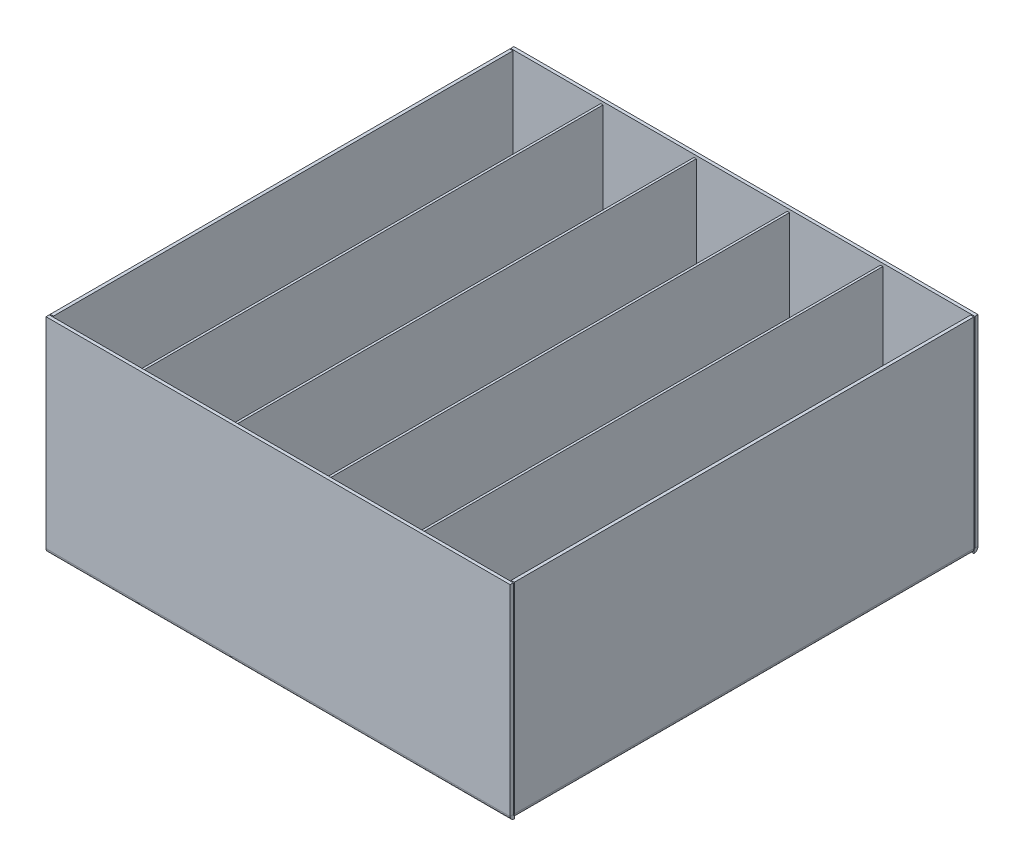
SolidWorks part; units mm, degrees
note: The reader was unsure of these and kept them because the rebuilt part matched: flange length of "Edge-Flange1", "Edge-Flange2", "Edge-Flange3".
material "6061-T6 (SS)"
ref_plane "Front Plane" through (0, 0, 0) normal (0, 0, 1) x (1, 0, 0)
ref_plane "Top Plane" through (0, 0, 0) normal (0, 1, 0) x (1, 0, 0)
ref_plane "Right Plane" through (0, 0, 0) normal (1, 0, 0) x (0, 0, -1)
sketch "Sketch1" plane through (0, 0, 0) normal (0, 1, 0) x (1, 0, 0)
  line L1 (-208.5546, 186.4198) -> (255.6454, 186.4198)
  line L2 (-208.5546, 186.4198) -> (-208.5546, -281.5802)
  line L3 (-208.5546, -281.5802) -> (255.6454, -281.5802)
  line L4 (255.6454, 186.4198) -> (255.6454, -281.5802)
  dimension "D1" = 464.2
  dimension "D2" = 468
base flange "Base-Flange1" sketch "Sketch1" thickness 3.2 reverse thickness direction no parameters "D1"=1
edge flange "Edge-Flange1" sketch "Sketch8" flange angle 90 flange length 205 flange position material inside bend radius 1 thickness 3.2 relief rectangular parameters "D6"=10
sketch "Sketch8" plane through (0, 0, -186.4198) normal (0, 0, -1) x (-1, 0, 0)
  line L0 (-255.6454, 0) -> (208.5546, 0) construction
  line L1 (-255.6454, 0) -> (208.5546, 0)
  line L2 (-255.6454, 0) -> (-255.6454, 201.8)
  line L3 (-255.6454, 201.8) -> (208.5546, 201.8)
  line L4 (208.5546, 201.8) -> (208.5546, 0)
bend "EdgeBend1" bend radius 1 bend angle 90 parameters "D5"=1
edge flange "Edge-Flange2" sketch "Sketch11" flange angle 90 flange length 205 bend radius 1 thickness 3.2 relief rectangular parameters "D6"=10
sketch "Sketch11" plane through (0, 0, 281.5802) normal (0, 0, 1) x (1, 0, 0)
  line L0 (-208.5546, 0) -> (255.6454, 0) construction
  line L1 (-208.5546, 0) -> (255.6454, 0)
  line L2 (-208.5546, 0) -> (-208.5546, 201.8)
  line L3 (-208.5546, 201.8) -> (255.6454, 201.8)
  line L4 (255.6454, 201.8) -> (255.6454, 0)
bend "EdgeBend2" bend radius 1 bend angle 90 parameters "D5"=2
sketch "Sketch12" plane through (0, 0, 0) normal (0, 1, 0) x (1, 0, 0)
  line L0 (-208.5546, 182.2198) -> (255.6454, 182.2198) construction
  line L1 (162.3454, 182.2198) -> (164.6454, 182.2198)
  line L2 (162.3454, 182.2198) -> (162.3454, -277.3802)
  line L3 (162.3454, -277.3802) -> (164.6454, -277.3802)
  line L4 (164.6454, 182.2198) -> (164.6454, -277.3802)
  line L5 (255.6454, -277.3802) -> (-208.5546, -277.3802) construction
  line L6 (255.6454, -277.3802) -> (255.6454, 182.2198) construction
  line L7 (255.6454, -281.5802) -> (-208.5546, -281.5802) construction
  line L8 (69.0454, 182.2198) -> (71.3454, 182.2198)
  line L9 (69.0454, 182.2198) -> (69.0454, -280.5802)
  line L10 (69.0454, -280.5802) -> (71.3454, -280.5802)
  line L11 (71.3454, 182.2198) -> (71.3454, -280.5802)
  line L12 (-21.9546, 182.2198) -> (-24.2546, 182.2198)
  line L13 (-21.9546, 182.2198) -> (-21.9546, -281.5802)
  line L14 (-21.9546, -281.5802) -> (-24.2546, -281.5802)
  line L15 (-24.2546, 182.2198) -> (-24.2546, -281.5802)
  line L17 (-115.2546, 182.2198) -> (-117.5546, 182.2198)
  line L18 (-115.2546, 182.2198) -> (-115.2546, -281.5802)
  line L19 (-115.2546, -281.5802) -> (-117.5546, -281.5802)
  line L20 (-117.5546, 182.2198) -> (-117.5546, -281.5802)
  dimension "D1" = 2.3
  dimension "D2" = 91
  dimension "D3" = 2.3
  dimension "D4" = 2.3
  dimension "D5" = 2.3
  dimension "D6" = 91
  dimension "D7" = 91
  dimension "D8" = 91
extrude "Boss-Extrude1" add sketch "Sketch12" along normal blind 200
edge flange "Edge-Flange3" sketch "Sketch17" flange profiles "Sketch17", "Sketch18" flange angle 90 flange length 205 flange position material inside bend radius 1 thickness 3.2 relief none parameters "D6"=10, "D8"=1
sketch "Sketch17" plane through (255.6454, 0, 0) normal (1, 0, 0) x (0, 0, -1)
  line L0 (-277.3802, 0) -> (182.2198, 0) construction
  line L1 (-277.3802, 0) -> (182.2198, 0)
  line L2 (-277.3802, 0) -> (-277.3802, 201.8)
  line L3 (-277.3802, 201.8) -> (182.2198, 201.8)
  line L4 (182.2198, 201.8) -> (182.2198, 0)
sketch "Sketch18" plane through (-208.5546, 0, 0) normal (-1, 0, 0) x (0, 0, 1)
  line L0 (-182.2198, 0) -> (277.3802, 0) construction
  line L1 (-182.2198, 0) -> (277.3802, 0)
  line L2 (-182.2198, 0) -> (-182.2198, 201.8)
  line L3 (-182.2198, 201.8) -> (277.3802, 201.8)
  line L4 (277.3802, 201.8) -> (277.3802, 0)
bend "EdgeBend3" bend radius 1 bend angle 90 parameters "D5"=3
bend "EdgeBend4" bend radius 1 bend angle 90 parameters "D5"=4
sketch "Bend-Lines1" [suppressed] plane through (0, 0, 0) normal (0, 1, 0) x (1, 0, 0)
sketch "Bounding-Box1" [suppressed] plane through (0, 0, 0) normal (0, 1, 0) x (1, 0, 0)
sheet metal parameters "Sheet-Metal1" thickness 3.2 parameters "D1"=1
flat pattern "Flat-Pattern1" [suppressed]
sketch "Bend-Lines2" plane through (0, 0, 0) normal (0, 1, 0) x (1, 0, 0)
sketch3d "Bounding-Box2" [suppressed]
  line L0 (212.1546, 186.4198, 0) -> (212.1546, -281.5802, 0) construction
  line L1 (-255.6454, 186.4198, 0) -> (-255.6454, -281.5802, 0) construction
  line L2 (212.1546, 186.4198, 0) -> (-255.6454, 186.4198, 0) construction
  line L3 (212.1546, -281.5802, 0) -> (-255.6454, -281.5802, 0) construction
sheet metal parameters "Sheet-Metal2" thickness 3.2 parameters "D1"=1
flat pattern "Flat-Pattern1"
sketch "Bend-Lines2" plane through (0, 0, 0) normal (0, 1, 0) x (1, 0, 0)
  line L0 (255.6454, 187.4619) -> (-212.1546, 187.4619) construction
  line L1 (255.6454, 187.4619) -> (-212.1546, 187.4619) construction
sketch3d "Bounding-Box2" [suppressed]
  line L0 (-212.1546, 365.3039, 0) -> (-212.1546, -281.5802, 0) construction
  line L1 (255.6454, 365.3039, 0) -> (255.6454, -281.5802, 0) construction
  line L2 (-212.1546, 365.3039, 0) -> (255.6454, 365.3039, 0) construction
  line L3 (-212.1546, -281.5802, 0) -> (255.6454, -281.5802, 0) construction
bend of the flat pattern "Flatten-<EdgeBend1>1"
sheet metal parameters "Sheet-Metal3" thickness 3.2 parameters "D1"=1
flat pattern "Flat-Pattern1"
sketch "Bend-Lines2" plane through (0, 0, 0) normal (0, 1, 0) x (1, 0, 0)
  line L0 (255.6454, 187.4619) -> (-208.5546, 187.4619) construction
  line L1 (255.6454, 187.4619) -> (-208.5546, 187.4619) construction
  line L2 (-208.5546, -282.6222) -> (255.6454, -282.6222) construction
  line L3 (-208.5546, -282.6222) -> (255.6454, -282.6222) construction
sketch3d "Bounding-Box2" [suppressed]
  line L0 (-208.5546, 365.3039, 0) -> (-208.5546, -460.4642, 0) construction
  line L1 (255.6454, 365.3039, 0) -> (255.6454, -460.4642, 0) construction
  line L2 (-208.5546, 365.3039, 0) -> (255.6454, 365.3039, 0) construction
  line L3 (-208.5546, -460.4642, 0) -> (255.6454, -460.4642, 0) construction
bend of the flat pattern "Flatten-<EdgeBend1>1"
bend of the flat pattern "Flatten-<EdgeBend2>1"
sheet metal parameters "Sheet-Metal4" thickness 3.2 parameters "D1"=1
flat pattern "Flat-Pattern1"
sketch "Bend-Lines2" plane through (0, 0, 0) normal (0, 1, 0) x (1, 0, 0)
  line L0 (255.6454, 187.4619) -> (-208.5546, 187.4619) construction
  line L1 (255.6454, 187.4619) -> (-208.5546, 187.4619) construction
  line L2 (-208.5546, -282.6222) -> (255.6454, -282.6222) construction
  line L3 (-208.5546, -282.6222) -> (255.6454, -282.6222) construction
sketch3d "Bounding-Box2" [suppressed]
  line L0 (-208.5546, 365.3039, 0) -> (-208.5546, -460.4642, 0) construction
  line L1 (255.6454, 365.3039, 0) -> (255.6454, -460.4642, 0) construction
  line L2 (-208.5546, 365.3039, 0) -> (255.6454, 365.3039, 0) construction
  line L3 (-208.5546, -460.4642, 0) -> (255.6454, -460.4642, 0) construction
bend of the flat pattern "Flatten-<EdgeBend1>1"
bend of the flat pattern "Flatten-<EdgeBend2>1"
sheet metal parameters "Sheet-Metal5" thickness 3.2 parameters "D1"=1
flat pattern "Flat-Pattern1"
sketch "Bend-Lines2" plane through (0, 0, 0) normal (0, 1, 0) x (1, 0, 0)
  line L0 (255.6454, 187.4619) -> (-208.5546, 187.4619) construction
  line L1 (255.6454, 187.4619) -> (-208.5546, 187.4619) construction
  line L2 (-208.5546, -282.6222) -> (255.6454, -282.6222) construction
  line L3 (-208.5546, -282.6222) -> (255.6454, -282.6222) construction
sketch3d "Bounding-Box2" [suppressed]
  line L0 (-208.5546, 365.3039, 0) -> (-208.5546, -460.4642, 0) construction
  line L1 (255.6454, 365.3039, 0) -> (255.6454, -460.4642, 0) construction
  line L2 (-208.5546, 365.3039, 0) -> (255.6454, 365.3039, 0) construction
  line L3 (-208.5546, -460.4642, 0) -> (255.6454, -460.4642, 0) construction
bend of the flat pattern "Flatten-<EdgeBend1>1"
bend of the flat pattern "Flatten-<EdgeBend2>1"
bend of the flat pattern "Flatten-<EdgeBend3>1"
bend of the flat pattern "Flatten-<EdgeBend4>1"
